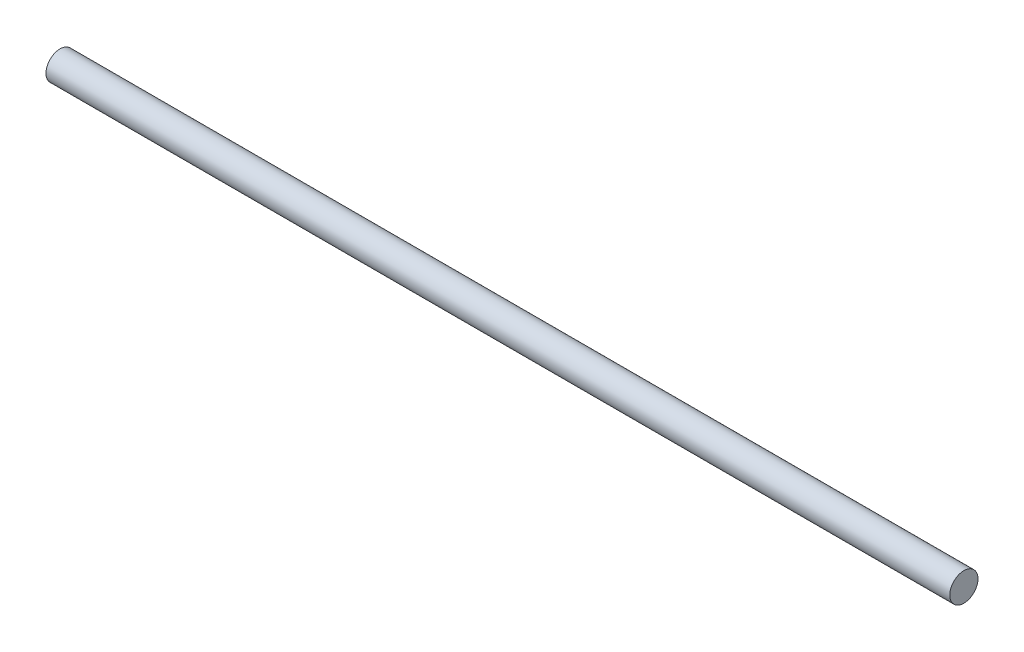
SolidWorks part; units mm, degrees
material "Copper"
ref_plane "Front Plane" through (0, 0, 0) normal (0, 0, 1) x (1, 0, 0)
ref_plane "Top Plane" through (0, 0, 0) normal (0, 1, 0) x (1, 0, 0)
ref_plane "Right Plane" through (0, 0, 0) normal (1, 0, 0) x (0, 0, -1)
sketch "Sketch1" plane through (0, 0, 0) normal (1, 0, 0) x (0, 0, -1)
  circle A0 centre (0, 0) radius 1.5875
  dimension "D1" = 3.175
extrude "Boss-Extrude1" add sketch "Sketch1" along normal blind 50.8 and the other way blind 50.8
